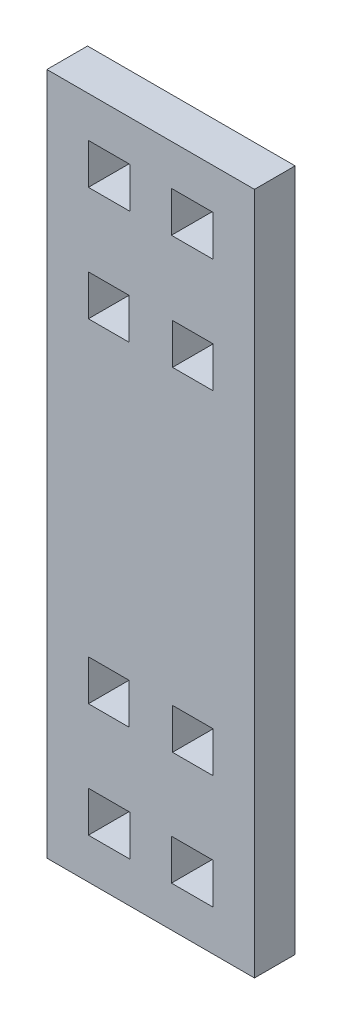
SolidWorks part; units mm, degrees
ref_plane "Front Plane" through (0, 0, 0) normal (0, 0, 1) x (1, 0, 0)
ref_plane "Top Plane" through (0, 0, 0) normal (0, 1, 0) x (1, 0, 0)
ref_plane "Right Plane" through (0, 0, 0) normal (1, 0, 0) x (0, 0, -1)
sketch "Sketch1" plane through (0, 0, 0) normal (0, 0, 1) x (1, 0, 0)
  line L1 (0, 0) -> (25.53, 0)
  line L2 (0, 0) -> (0, 84)
  line L3 (0, 84) -> (25.53, 84)
  line L4 (25.53, 0) -> (25.53, 84)
  dimension "D1" = 84
  dimension "D2" = 25.53
extrude "Boss-Extrude1" add sketch "Sketch1" along normal blind 5
sketch "Sketch2" plane through (0, 0, 5) normal (0, 0, 1) x (1, 0, 0)
  line L0 (25.53, 42) -> (-8.1809, 42) construction
  line L1 (2.75, 0) -> (-2.75, 0) construction
  line L2 (20.424, 69.3685) -> (25.53, 69.3685) construction
  line L3 (5.106, 79) -> (10.212, 79)
  line L4 (5.106, 79) -> (5.106, 74)
  line L5 (5.106, 74) -> (10.212, 74)
  line L6 (10.212, 79) -> (10.212, 74)
  line L7 (15.318, 79) -> (20.424, 79)
  line L8 (15.318, 79) -> (15.318, 74)
  line L9 (15.318, 74) -> (20.424, 74)
  line L10 (20.424, 79) -> (20.424, 74)
  line L11 (25.53, 0) -> (25.53, 84) construction
  line L12 (20.4532, 19) -> (20.4532, 24)
  line L13 (5.106, 70.4299) -> (0, 70.4299) construction
  line L14 (0, -2.75) -> (0, 2.75) construction
  line L15 (25.53, 84) -> (0, 84) construction
  line L16 (5.106, 65) -> (10.106, 65)
  line L17 (5.106, 65) -> (5.106, 60)
  line L18 (5.106, 60) -> (10.106, 60)
  line L19 (10.106, 65) -> (10.106, 60)
  line L20 (15.4532, 65) -> (20.4532, 65)
  line L21 (15.4532, 65) -> (15.4532, 60)
  line L22 (15.4532, 60) -> (20.4532, 60)
  line L23 (20.4532, 65) -> (20.4532, 60)
  line L24 (15.4532, 24) -> (20.4532, 24)
  line L25 (15.4532, 19) -> (15.4532, 24)
  line L26 (15.4532, 19) -> (20.4532, 19)
  line L27 (10.106, 19) -> (10.106, 24)
  line L28 (5.106, 24) -> (10.106, 24)
  line L29 (5.106, 19) -> (5.106, 24)
  line L30 (5.106, 19) -> (10.106, 19)
  line L44 (20.424, 5) -> (20.424, 10)
  line L45 (15.318, 10) -> (20.424, 10)
  line L46 (15.318, 5) -> (20.424, 5)
  line L47 (10.212, 5) -> (10.212, 10)
  line L48 (5.106, 5) -> (10.212, 5)
  line L49 (5.106, 5) -> (5.106, 10)
  line L50 (5.106, 10) -> (10.212, 10)
  line L51 (15.318, 5) -> (15.318, 10)
  dimension "D1" = 5
  dimension "D2" = 5
  dimension "D3" = 5
  dimension "D4" = 5
  dimension "D5" = 5
  dimension "D6" = 18
extrude "Cut-Extrude1" cut sketch "Sketch2" against normal through all
